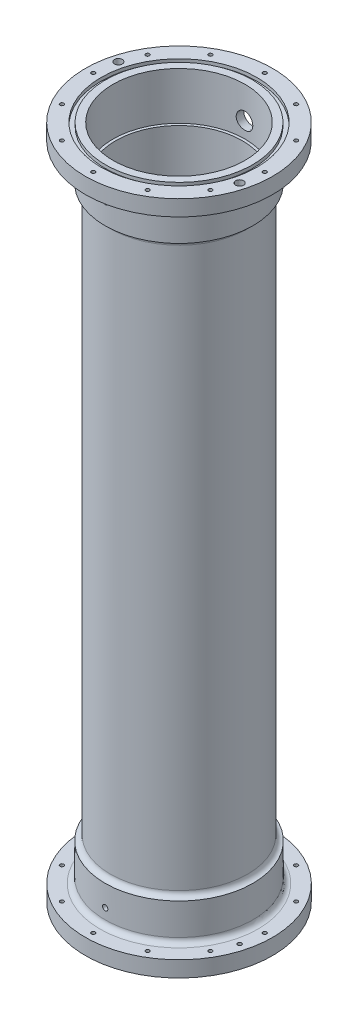
SolidWorks part; units mm, degrees
material "6061-T6 (SS)"
ref_plane "Front Plane" through (0, 0, 0) normal (0, 0, 1) x (1, 0, 0)
ref_plane "Top Plane" through (0, 0, 0) normal (0, 1, 0) x (1, 0, 0)
ref_plane "Right Plane" through (0, 0, 0) normal (1, 0, 0) x (0, 0, -1)
sketch "Sketch2" plane through (0, 0, 0) normal (0, 1, 0) x (1, 0, 0)
  circle A0 centre (0, 0) radius 38.1
  circle A1 centre (0, 0) radius 41.275
  dimension "D1" = 82.55
  dimension "D2" = 76.2
extrude "Base Cylinder" add sketch "Sketch2" along normal blind 406.4
sketch "Sketch3" plane through (0, 0, 0) normal (0, -1, 0) x (1, 0, 0)
  circle A0 centre (0, 0) radius 38.1
  circle A1 centre (0, 0) radius 56.3562
  dimension "D1" = 112.7125
extrude "Aft Flange" add sketch "Sketch3" against normal blind 9.525
sketch "Sketch34" plane through (0, 0, 0) normal (0, -1, 0) x (1, 0, 0)
  circle A0 centre (0, 0) radius 39.75
  dimension "D1" = 79.5
extrude "TemperatureInsert" cut sketch "Sketch34" against normal blind 28.575
sketch "Sketch6" plane through (0, 0, 0) normal (0, -1, 0) x (1, 0, 0)
  circle A0 centre (0, 0) radius 46.9011
  circle A1 centre (0, 0) radius 44.2849
  dimension "D1" = 93.8022
  dimension "D2" = 88.5698
extrude "Aft O-Ring" cut sketch "Sketch6" against normal blind 1.9812
sketch "Sketch33" plane through (0, 9.525, 0) normal (0, 1, 0) x (1, 0, 0)
  circle A0 centre (0, 0) radius 41.275
  circle A1 centre (0, 0) radius 44.45
  dimension "D1" = 82.55
  dimension "D2" = 88.9
extrude "CriticalBoss" add sketch "Sketch33" along normal blind 22.225
fillet "Fillet1" radius 3.175 2 edges at (0, 9.525, -44.45) (0, 31.75, 41.275)
sketch "Sketch For Bolt Holes" plane through (0, 0, 0) normal (0, -1, 0) x (1, 0, 0)
  circle A0 centre (-51.6255, 0) radius 1.5875
  circle A1 centre (-44.709, 25.8128) radius 1.5875
  circle A2 centre (-25.8128, 44.709) radius 1.5875
  circle A3 centre (0, 51.6255) radius 1.5875
  circle A4 centre (25.8127, 44.709) radius 1.5875
  circle A5 centre (44.709, 25.8128) radius 1.5875
  circle A6 centre (51.6255, 0) radius 1.5875
  circle A7 centre (44.709, -25.8127) radius 1.5875
  circle A8 centre (25.8128, -44.709) radius 1.5875
  circle A9 centre (0, -51.6255) radius 1.5875
  circle A10 centre (-25.8127, -44.709) radius 1.5875
  circle A11 centre (-44.709, -25.8128) radius 1.5875
  point P36 (0, 0)
  dimension "D2" = 3.175
  dimension "D1" = 51.6255
  dimension "D3" = 12
hole_wizard "Bolt Circle" positions "Sketch8" profile "Sketch9" hole size "#4-40" standard "ANSI Inch"
sketch "Sketch8" plane through (0, 0, 0) normal (0, -1, 0) x (-1, 0, 0)
  point P0 (-25.8127, -44.709)
  point P3 (-44.709, -25.8128)
  point P6 (-51.6255, 0)
  point P9 (-44.709, 25.8127)
  point P12 (-25.8128, 44.709)
  point P15 (0, 51.6255)
  point P18 (25.8127, 44.709)
  point P21 (44.709, 25.8128)
  point P24 (51.6255, 0)
  point P27 (44.709, -25.8128)
  point P30 (25.8128, -44.709)
  point P33 (0, -51.6255)
  point P36 (-25.8127, -44.709)
  point P38 (-44.709, -25.8128)
  point P40 (-51.6255, 0)
sketch "Sketch9" plane through (25.8127, 0, 44.709) normal (1, 0, 0) x (0, 0, -1)
  line L0 (0, 0) -> (0, 26.0792)
  line L1 (0, 26.0792) -> (1.1303, 25.4)
  line L2 (1.1303, 25.4) -> (1.1303, 0)
  line L5 (1.1303, 0) -> (0, 0)
  line L10 (0, 26.0792) -> (-1.1303, 25.4) construction
  line L11 (0, -6.35) -> (0, 107.95) construction
  dimension "Hole Dia." = 2.2606
  dimension "Hole Depth" = 25.4
  dimension "Drill Angle" = 118
sketch "Dowel Hole Sketch" plane through (0, 0, 0) normal (0, -1, 0) x (1, 0, 0)
  line L0 (0, 0) -> (-51.6255, 0) construction
  line L1 (0, 0) -> (-49.8664, -13.3617) construction
  line L2 (0, 0) -> (0, -51.6255) construction
  line L3 (0, 0) -> (49.8664, 13.3617) construction
  circle A0 centre (0, 0) radius 51.6255
  circle A1 centre (-49.8664, -13.3617) radius 4.6172
  circle A2 centre (49.8664, 13.3617) radius 3.4532
  dimension "D1" = 15
hole_wizard "3/16 (0.1875) Press Dowel Hole1" positions "Sketch14" profile "Sketch12" hole size "3/16" standard "ANSI Inch"
sketch "Sketch14" plane through (0, 0, 0) normal (0, -1, 0) x (-1, 0, 0)
  point P0 (49.8664, 13.3617)
  point P3 (-49.8664, -13.3617)
sketch "Sketch12" plane through (-49.8664, 0, -13.3617) normal (1, 0, 0) x (0, 0, -1)
  line L0 (0, 0) -> (0, 7.7808)
  line L1 (0, 7.7808) -> (2.3812, 6.35)
  line L2 (2.3812, 6.35) -> (2.3812, 0)
  line L5 (2.3812, 0) -> (0, 0)
  line L10 (0, 7.7808) -> (-2.3813, 6.35) construction
  line L11 (0, -6.35) -> (0, 107.95) construction
  dimension "Hole Dia." = 4.7625
  dimension "Hole Depth" = 6.35
  dimension "Drill Angle" = 118
hole_wizard "3/32 (0.09375) Diameter Hole1" positions "Sketch19" profile "Sketch21" hole size "3/32" standard "ANSI Inch" end condition up to next
sketch "Sketch19" plane through (0, 0, 0) normal (0, -1, 0) x (-1, 0, 0)
  point P0 (-49.8664, -13.3617)
  point P3 (49.8664, 13.3617)
sketch "Sketch21" plane through (49.8664, 0, 13.3617) normal (1, 0, 0) x (0, 0, -1)
  line L0 (0, 0) -> (0, 398.6192)
  line L1 (0, 398.6192) -> (1.1906, 398.6192)
  line L2 (1.1906, 398.6192) -> (1.1906, 0)
  line L5 (1.1906, 0) -> (0, 0)
  line L11 (0, -6.35) -> (0, 107.95) construction
  dimension "Thru Hole Dia." = 2.3812
  dimension "Thru Hole Depth" = 398.6192
ref_plane "Hoop Mid-Plane" through (0, 203.2, 0) normal (0, 1, 0) x (1, 0, 0)
ref_plane "PressureTapHolePlane" through (0, 0, 44.45) normal (0, 0, 1) x (1, 0, 0)
ref_plane "TemperatureTapPlane" through (0, 0, -44.45) normal (0, 0, 1) x (1, 0, 0)
sketch "Sketch35" plane through (0, 0, 44.45) normal (0, 0, 1) x (1, 0, 0)
  line L0 (-56.3562, 0) -> (56.3562, 0) construction
  circle A0 centre (0, 19.05) radius 1.5875
  dimension "D1" = 19.05
  dimension "D2" = 3.175
extrude "Pressure Tap Aft Big" cut sketch "Sketch35" against normal blind 2.3813
sketch "Sketch41" plane through (0, 0, 42.0687) normal (0, 0, 1) x (1, 0, 0)
  circle A0 centre (0, 19.05) radius 0.1984
extrude "Pressure Tap Aft Small" cut sketch "Sketch41" against normal up to next
sketch "ThermoHole" plane through (0, 0, -44.45) normal (0, 0, 1) x (1, 0, 0)
  line L0 (-56.3562, 0) -> (56.3562, 0) construction
  circle A0 centre (0, 19.05) radius 3.175
  dimension "D1" = 19.05
  dimension "D2" = 6.35
hole_wizard "1/8 NPT Tapped ThermocoupleHole" positions "Sketch43" profile "Sketch44" size "1/8" standard "ANSI Inch"
sketch "Sketch43" plane through (0, 0, -44.45) normal (0, 0, 1) x (1, 0, 0)
  point P0 (0, 19.05)
sketch "Sketch44" plane through (0, 19.05, -44.45) normal (1, 0, 0) x (0, 1, 0)
  line L0 (0, 0) -> (0, 14.2175)
  line L1 (4.2164, 11.684) -> (0, 14.2175)
  line L2 (-4.2164, 11.684) -> (0, 14.2175) construction
  line L3 (4.2164, 11.684) -> (4.2164, 6.858)
  line L4 (4.2164, 6.858) -> (4.9362, 6.858)
  line L5 (4.9362, 6.858) -> (5.1415, 0)
  line L6 (-4.9362, 6.858) -> (-5.1415, 0) construction
  line L7 (5.1415, 0) -> (0, 0)
  line L8 (0, -6.35) -> (0, 107.95) construction
  line L11 (-4.2164, 6.858) -> (-4.9362, 6.858) construction
  dimension "Tap Drill Dia." = 8.4328
  dimension "Tap Drill Depth" = 11.684
  dimension "Thread Dia." = 10.283
  dimension "Thread Angle" = 3.43
  dimension "Thread Depth" = 6.858
  dimension "Drill Angle" = 118
mirror "Mirror1" about plane through (0, 203.2, 0) normal (0, 1, 0) of "1/8 NPT Tapped ThermocoupleHole", "Fillet1", "Aft Flange", "TemperatureInsert", "Aft O-Ring", "CriticalBoss", "Bolt Circle", "3/16 (0.1875) Press Dowel Hole1", "3/32 (0.09375) Diameter Hole1", "Pressure Tap Aft Big", "Pressure Tap Aft Small"
